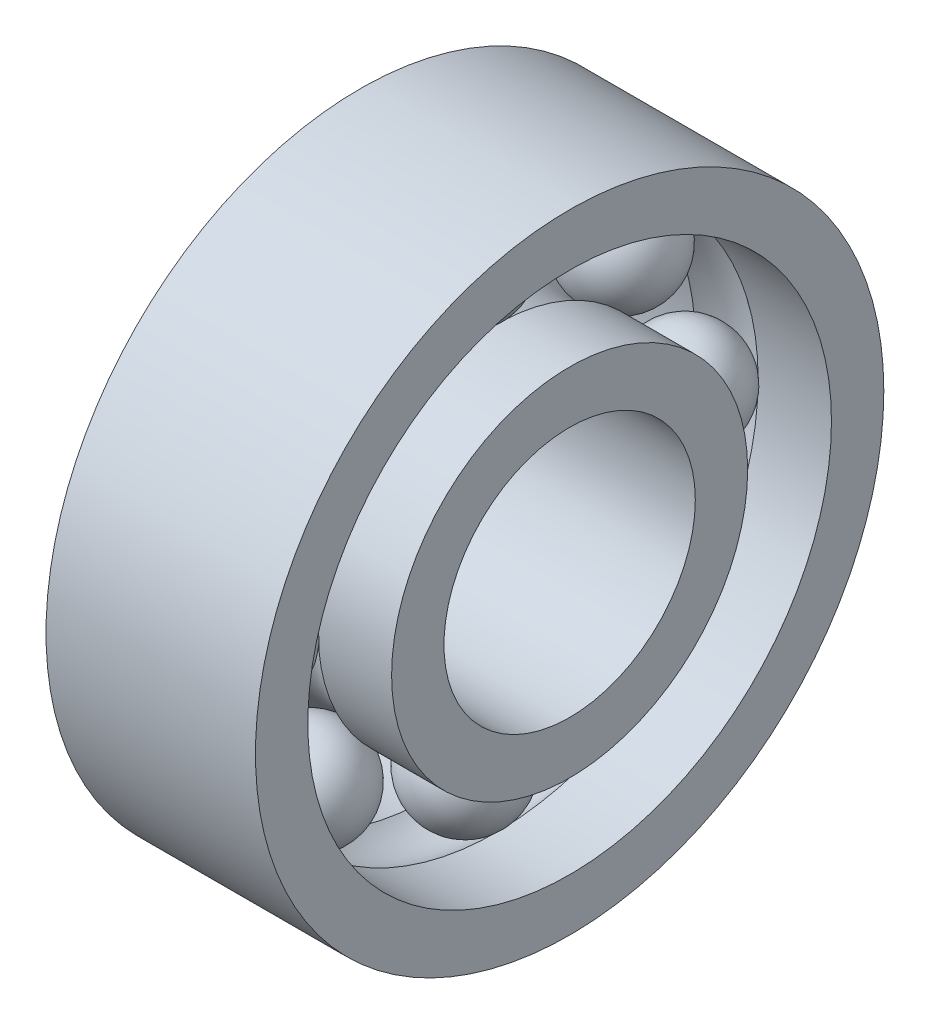
SolidWorks part; units mm, degrees
ref_plane "Front Plane" through (0, 0, 0) normal (0, 0, 1) x (1, 0, 0)
ref_plane "Top Plane" through (0, 0, 0) normal (0, 1, 0) x (1, 0, 0)
ref_plane "Right Plane" through (0, 0, 0) normal (1, 0, 0) x (0, 0, -1)
ref_axis "Axis1" through (88.99, 0, 0) along (-1, 0, 0)
sketch "Sketch1" plane through (0, 0, 0) normal (0, 0, 1) x (1, 0, 0)
  line L0 (2.5, 7.5) -> (2.5, 3) construction
  line L1 (0, 4.25) -> (1.75, 4.25)
  line L2 (0, 4.25) -> (0, 3)
  line L3 (0, 3) -> (5, 3)
  line L4 (5, 4.25) -> (5, 3)
  line L5 (0, 7.5) -> (5, 7.5)
  line L6 (0, 7.5) -> (0, 6.25)
  line L7 (0, 6.25) -> (1.75, 6.25)
  line L8 (5, 7.5) -> (5, 6.25)
  line L9 (88.99, 0) -> (-88.99, 0) construction
  line L10 (3.25, 6.25) -> (5, 6.25)
  line L11 (3.25, 4.25) -> (5, 4.25)
  circle A0 centre (2.5, 5.25) radius 1.25
  point P19 (1.75, 5)
  point P20 (3.25, 7)
  point P21 (1.75, 4.25)
  point P22 (3.25, 6.25)
  dimension "D4" = 2.5
  dimension "D1" = 6
  dimension "D2" = 15
  dimension "D3" = 5
  dimension "D5" = 1.25
revolve "Revolve1" add sketch "Sketch1" angle 360 about axis through (88.99, 0, 0) along (-1, 0, 0) region at (3.7911, 6.8973, 0) region at (1.2089, 6.8973, 0) region at (3.7911, 3.6027, 0) region at (1.2089, 3.6027, 0)
revolve "Revolve2" add sketch "Sketch1<3>" angle 360 about L0 region at (1.9695, 5.25, 0)
sketch "Sketch1<3>" plane through (0, 0, 0) normal (0, 0, 1) x (1, 0, 0) same geometry as "Sketch1"
pattern_circular "CirPattern2" count 8 over 360 about axis through (88.99, 0, 0) along (-1, 0, 0) reverse direction yes of bodies 103
equation "\"Di\" = 6mm"
equation "\"Do\" = 15mm"
equation "\"L\" = 5mm"
equation "\"Dk\"= 2.5mm"
equation "\"D1@Sketch1\"=\"Di\""
equation "\"D2@Sketch1\"=\"Do\""
equation "\"D4@Sketch1\"=\"Dk\""
equation "\"D3@Sketch1\"=\"L\""
